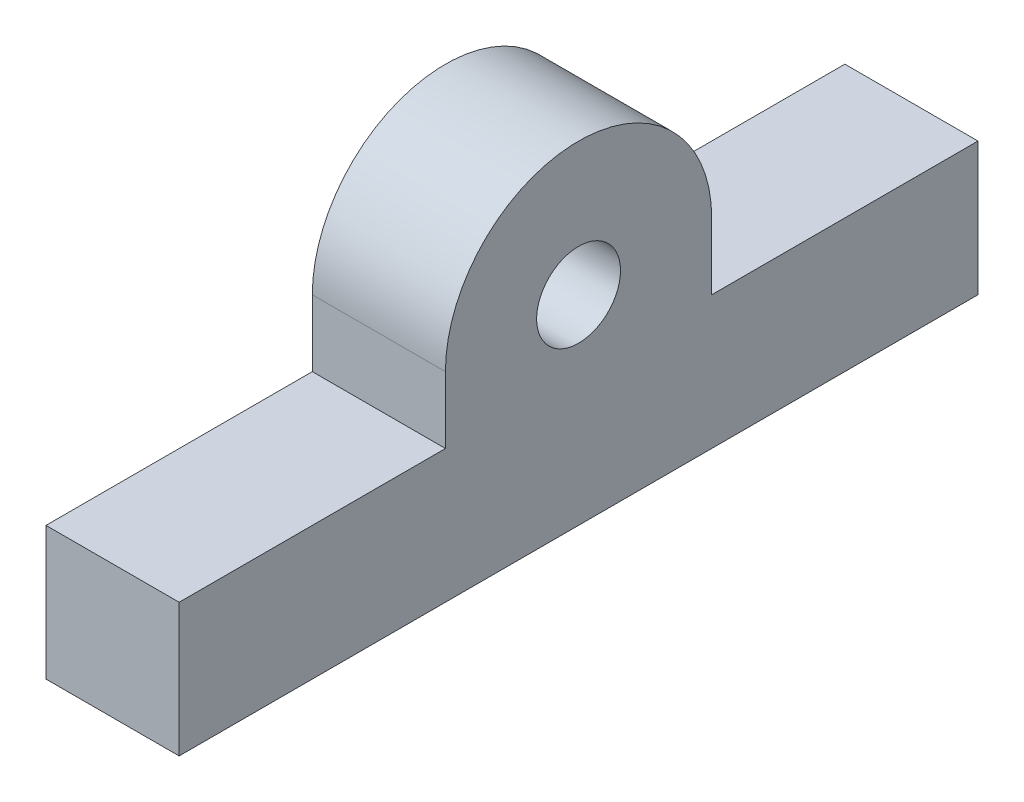
SolidWorks part; units mm, degrees
ref_plane "Front Plane" through (0, 0, 0) normal (0, 0, 1) x (1, 0, 0)
ref_plane "Top Plane" through (0, 0, 0) normal (0, 1, 0) x (1, 0, 0)
ref_plane "Right Plane" through (0, 0, 0) normal (1, 0, 0) x (0, 0, -1)
sketch "Sketch1" plane through (0, 0, 0) normal (1, 0, 0) x (0, 0, -1)
  line L0 (0, 0) -> (76.2, 0)
  line L1 (76.2, 0) -> (76.2, 12.7)
  line L2 (76.2, 12.7) -> (50.8, 12.7)
  line L3 (0, 12.7) -> (0, 0)
  line L5 (50.8, 12.7) -> (50.8, 19.05)
  line L7 (25.4, 19.05) -> (25.4, 12.7)
  line L9 (25.4, 12.7) -> (0, 12.7)
  arc A0 (50.8, 19.05) -> (25.4, 19.05) centre (38.1, 19.05) ccw
  dimension "D1" = 76.2
  dimension "D2" = 12.7
  dimension "D3" = 25.4
  dimension "D4" = 25.4
  dimension "D5" = 6.35
extrude "Boss-Extrude1" add sketch "Sketch1" along normal blind 12.7
sketch "Sketch2" plane through (12.7, 0, 0) normal (1, 0, 0) x (0, 0, -1)
  line L0 (0, 0) -> (76.2, 0) construction
  circle A0 centre (38.1, 19.05) radius 4
  dimension "D1" = 8
extrude "Cut-Extrude1" cut sketch "Sketch2" against normal through all
sketch "Sketch3" plane through (0, 0, 0) normal (0, -1, 0) x (1, 0, 0)
  line L0 (12.7, -76.2) -> (0, -76.2) construction
  line L3 (12.7, 0) -> (0, 0) construction
  circle A0 centre (6.35, -12.7) radius 2
  circle A1 centre (6.35, -63.5) radius 2
  point P4 (6.35, 0)
  point P10 (6.35, -76.2)
  dimension "D1" = 4
  dimension "D4" = 4
  dimension "D6" = 12.7
  dimension "D2" = 0
  dimension "D3" = 12.7
  dimension "D5" = 0
  dimension "D7" = 50.8
extrude "Cut-Extrude2" cut sketch "Sketch3" against normal blind 7
equation "\"bearing_d\"= 0.5in"
equation "\"heat_set_d\"= 0.1in"
